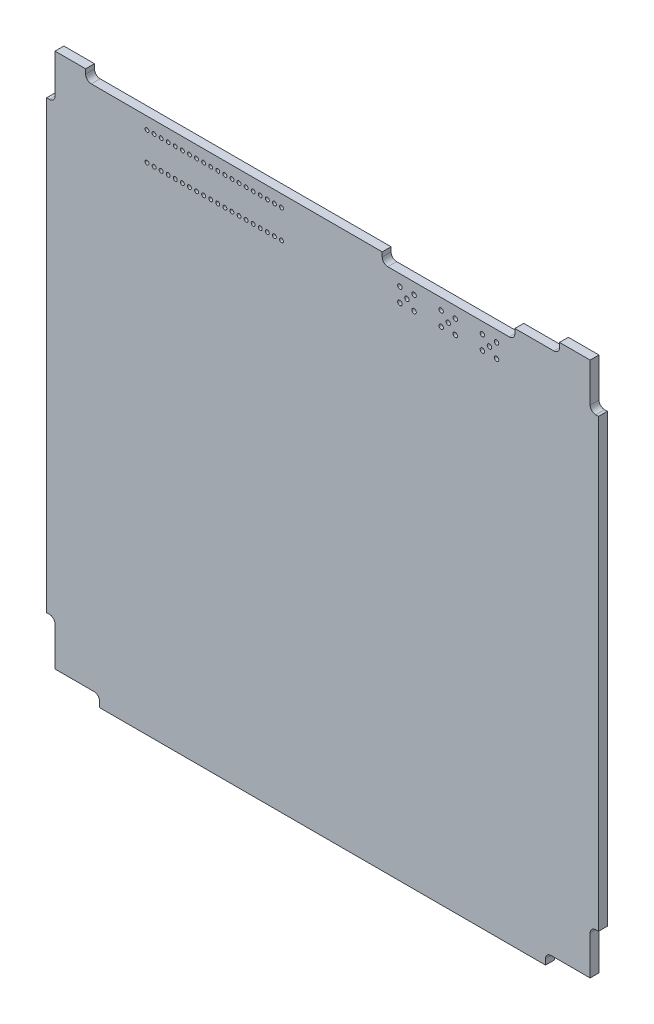
SolidWorks part; units mm, degrees
material "ABS"
ref_plane "Front Plane" through (0, 0, 0) normal (0, 0, 1) x (1, 0, 0)
ref_plane "Top Plane" through (0, 0, 0) normal (0, 1, 0) x (1, 0, 0)
ref_plane "Right Plane" through (0, 0, 0) normal (1, 0, 0) x (0, 0, -1)
sketch "Sketch1" plane through (0, 0, 0) normal (0, 0, 1) x (1, 0, 0)
  line L0 (-40, 50) -> (-40, 48)
  line L1 (-50, -50) -> (50, -50)
  line L2 (-50, -50) -> (-50, 50)
  line L3 (-50, 50) -> (50, 50)
  line L4 (50, -50) -> (50, 50)
  line L5 (-50, -50) -> (50, 50) construction
  line L6 (-50, 50) -> (50, -50) construction
  line L7 (-50, 50) -> (-40, 50)
  line L8 (-50, 50) -> (-50, 40)
  line L9 (-40, 48) -> (-48, 48)
  line L10 (-48, 48) -> (-48, 40)
  line L11 (50, 50) -> (40, 50)
  line L12 (50, 50) -> (50, 40)
  line L13 (-48, 40) -> (-50, 40)
  line L14 (50, 40) -> (48, 40)
  line L15 (-50, -50) -> (-37.8649, -50)
  line L16 (-50, -50) -> (-50, -37.8649)
  line L17 (50, 50) -> (50, 40)
  line L18 (50, 50) -> (40, 50)
  line L19 (50, -50) -> (41.5, -50)
  line L20 (50, -50) -> (50, -41.5)
  line L21 (48, 40) -> (48, 48)
  line L22 (48, 48) -> (40, 48)
  line L23 (40, 48) -> (40, 50)
  line L24 (40, -50) -> (40, -48)
  line L25 (50, -50) -> (40, -50)
  line L26 (50, -50) -> (50, -40)
  line L27 (40, -48) -> (48, -48)
  line L28 (48, -48) -> (48, -40)
  line L29 (48, -40) -> (50, -40)
  line L30 (-50, -40) -> (-48, -40)
  line L31 (-50, -50) -> (-50, -40)
  line L32 (-50, -50) -> (-40, -50)
  line L33 (-48, -40) -> (-48, -48)
  line L34 (-48, -48) -> (-40, -48)
  line L35 (-40, -48) -> (-40, -50)
  point P0 (0, 0)
  point P38 (0, 0)
  dimension "D1" = 100
  dimension "D2" = 100
  dimension "D3" = 2
  dimension "D4" = 10
  dimension "D5" = 4
extrude "Boss-Extrude1" add sketch "Sketch1" along normal blind 1.5875 contours L1 L4 L3 L2 region at (0, 0, 0)
sketch "Sketch2" plane through (0, 0, 1.5875) normal (0, 0, 1) x (1, 0, 0)
  line L0 (0, 50) -> (0, -50) construction
  line L1 (-40, 50) -> (40, 50) construction
  line L2 (-40, -50) -> (40, -50) construction
  line L3 (-50, -40) -> (-50, 40) construction
  line L4 (-40, 50) -> (40, 50) construction
  circle A0 centre (-31.5, 44) radius 0.35
  circle A1 centre (-30.23, 44) radius 0.35
  circle A2 centre (-28.96, 44) radius 0.35
  circle A3 centre (-27.69, 44) radius 0.35
  circle A4 centre (-26.42, 44) radius 0.35
  circle A5 centre (-25.15, 44) radius 0.35
  circle A6 centre (-23.88, 44) radius 0.35
  circle A7 centre (-22.61, 44) radius 0.35
  circle A8 centre (-21.34, 44) radius 0.35
  circle A9 centre (-20.07, 44) radius 0.35
  circle A10 centre (-18.8, 44) radius 0.35
  circle A11 centre (-17.53, 44) radius 0.35
  circle A12 centre (-16.26, 44) radius 0.35
  circle A13 centre (-14.99, 44) radius 0.35
  circle A14 centre (-13.72, 44) radius 0.35
  circle A15 centre (-12.45, 44) radius 0.35
  circle A16 centre (-11.18, 44) radius 0.35
  circle A17 centre (-9.91, 44) radius 0.35
  circle A18 centre (-8.64, 44) radius 0.35
  circle A19 centre (-7.37, 44) radius 0.35
  circle A20 centre (-30.23, 38.92) radius 0.35
  circle A21 centre (-28.96, 38.92) radius 0.35
  circle A22 centre (-27.69, 38.92) radius 0.35
  circle A23 centre (-26.42, 38.92) radius 0.35
  circle A24 centre (-25.15, 38.92) radius 0.35
  circle A25 centre (-23.88, 38.92) radius 0.35
  circle A26 centre (-22.61, 38.92) radius 0.35
  circle A27 centre (-21.34, 38.92) radius 0.35
  circle A28 centre (-20.07, 38.92) radius 0.35
  circle A29 centre (-18.8, 38.92) radius 0.35
  circle A30 centre (-17.53, 38.92) radius 0.35
  circle A31 centre (-16.26, 38.92) radius 0.35
  circle A32 centre (-14.99, 38.92) radius 0.35
  circle A33 centre (-13.72, 38.92) radius 0.35
  circle A34 centre (-12.45, 38.92) radius 0.35
  circle A35 centre (-11.18, 38.92) radius 0.35
  circle A36 centre (-9.91, 38.92) radius 0.35
  circle A37 centre (-8.64, 38.92) radius 0.35
  circle A38 centre (-7.37, 38.92) radius 0.35
  circle A39 centre (-31.5, 38.92) radius 0.35
  dimension "D1" = 0.7
  dimension "D4" = 18.5
  dimension "D5" = 6
  dimension "D2" = 5.08
  dimension "D3" = 1.27
extrude "Cut-Extrude1" cut sketch "Sketch2" against normal through all
sketch "Sketch3" plane through (0, 50, 0) normal (0, 1, 0) x (1, 0, 0)
  line L0 (-40, 0) -> (40, 0) construction
  line L1 (10.7, 0) -> (19.7, 0)
  line L2 (10.7, 0) -> (10.7, -1.5875)
  line L3 (10.7, -1.5875) -> (19.7, -1.5875)
  line L4 (-40, -1.5875) -> (-40, 0) construction
  line L5 (-40, -1.5875) -> (40, -1.5875) construction
  line L6 (15.2, 0) -> (15.2, -1.5875) construction
  line L7 (12, 0) -> (12, -1.5875) construction
  line L8 (18.4, 0) -> (18.4, -1.5875) construction
  line L9 (-40, -1.5875) -> (40, -1.5875) construction
  line L12 (19.7, 0) -> (34.5, 0)
  line L14 (19.7, -1.5875) -> (34.5, -1.5875)
  line L15 (34.5, 0) -> (34.5, -1.5875)
  dimension "D1" = 9
  dimension "D2" = 6.4
  dimension "D3" = 3.2
  dimension "D5" = 14.8
  dimension "D6" = 50.7
extrude "Cut-Extrude2" cut sketch "Sketch3" against normal blind 5.6475
fillet "Fillet2" radius 1 2 edges at (10.7, 44.3525, 0.7938) (34.5, 44.3525, 0.7937)
sketch "Sketch5" plane through (0, 0, 0) normal (0, 0, -1) x (-1, 0, 0)
  line L0 (40, -50) -> (-40, -50) construction
  line L1 (-49.5, 50) -> (49.5, 50)
  line L2 (-49.5, 50) -> (-49.5, -50)
  line L3 (-49.5, -50) -> (49.5, -50)
  line L4 (49.5, 50) -> (49.5, -50)
  line L5 (40, 50) -> (-10.7, 50) construction
  line L6 (50, -40) -> (50, 40) construction
  dimension "D1" = 99
  dimension "D2" = 0.5
extrude "Cut-Extrude3" cut sketch "Sketch5" against normal through all flip side to cut
sketch "Sketch6" plane through (0, 0, 1.5875) normal (0, 0, 1) x (1, 0, 0)
  line L0 (11.7, 44.3525) -> (33.5, 44.3525) construction
  line L1 (28.67, 39.8125) -> (31.21, 39.8125) construction
  line L2 (28.67, 39.8125) -> (28.67, 42.3525) construction
  line L3 (28.67, 42.3525) -> (31.21, 42.3525) construction
  line L4 (31.21, 39.8125) -> (31.21, 42.3525) construction
  line L5 (28.67, 39.8125) -> (31.21, 42.3525) construction
  line L6 (28.67, 42.3525) -> (31.21, 39.8125) construction
  line L7 (34.5, 45.3525) -> (34.5, 50) construction
  line L8 (21.27, 39.8125) -> (23.81, 39.8125) construction
  line L9 (21.27, 39.8125) -> (21.27, 42.3525) construction
  line L10 (21.27, 42.3525) -> (23.81, 42.3525) construction
  line L11 (23.81, 39.8125) -> (23.81, 42.3525) construction
  line L12 (21.27, 39.8125) -> (23.81, 42.3525) construction
  line L13 (21.27, 42.3525) -> (23.81, 39.8125) construction
  line L14 (13.87, 39.8125) -> (16.41, 39.8125) construction
  line L17 (13.87, 39.8125) -> (13.87, 42.3525) construction
  line L18 (13.87, 42.3525) -> (16.41, 42.3525) construction
  line L19 (16.41, 39.8125) -> (16.41, 42.3525) construction
  line L20 (13.87, 39.8125) -> (16.41, 42.3525) construction
  line L21 (13.87, 42.3525) -> (16.41, 39.8125) construction
  circle A0 centre (29.94, 41.0825) radius 0.4
  circle A1 centre (28.67, 42.3525) radius 0.4
  circle A2 centre (31.21, 42.3525) radius 0.4
  circle A3 centre (31.21, 39.8125) radius 0.4
  circle A4 centre (28.67, 39.8125) radius 0.4
  circle A5 centre (22.54, 41.0825) radius 0.4
  circle A6 centre (21.27, 42.3525) radius 0.4
  circle A7 centre (23.81, 42.3525) radius 0.4
  circle A8 centre (23.81, 39.8125) radius 0.4
  circle A9 centre (21.27, 39.8125) radius 0.4
  circle A10 centre (15.14, 41.0825) radius 0.4
  circle A11 centre (13.87, 42.3525) radius 0.4
  circle A12 centre (16.41, 42.3525) radius 0.4
  circle A13 centre (16.41, 39.8125) radius 0.4
  circle A14 centre (13.87, 39.8125) radius 0.4
  point P23 (27.2, 39.7784)
  point P32 (19.8, 39.7784)
  dimension "D1" = 2.54
  dimension "D2" = 0.8
  dimension "D3" = 2.54
  dimension "D4" = 3.27
  dimension "D5" = 4.56
  dimension "D6" = 7.4
  dimension "D8" = 2
  dimension "D7" = 3
sketch "Sketch7" plane through (0, 0, 1.5875) normal (0, 0, 1) x (1, 0, 0)
  line L0 (-40, 50) -> (-36.5, 50)
  line L1 (-40, 50) -> (10.7, 50) construction
  line L2 (-36.5, 50) -> (-36.5, 48)
  line L3 (-36.5, 48) -> (-41.5, 48)
  line L4 (-40, 48) -> (-48, 48) construction
  line L5 (-41.5, 48) -> (-41.5, 41.5)
  line L6 (-41.5, 41.5) -> (-42, 41.5)
  line L7 (-47, 36.5) -> (-47, -36.5)
  line L8 (-40, 50) -> (-49.5, 50)
  line L9 (-49.5, 50) -> (-49.5, -50)
  line L10 (-49.5, -40) -> (-49.5, 40) construction
  line L11 (49.5, 0) -> (-49.5, 0) construction
  line L12 (-40, -50) -> (-49.5, -50)
  line L13 (-41.5, -41.5) -> (-42, -41.5)
  line L14 (-41.5, -48) -> (-41.5, -41.5)
  line L15 (-36.5, -48) -> (-41.5, -48)
  line L16 (-36.5, -50) -> (-36.5, -48)
  line L17 (-40, -50) -> (-36.5, -50)
  line L18 (0, 0) -> (0, -14.0383) construction
  line L19 (40, -50) -> (36.5, -50)
  line L20 (36.5, -50) -> (36.5, -48)
  line L21 (36.5, -48) -> (41.5, -48)
  line L22 (41.5, -48) -> (41.5, -41.5)
  line L23 (41.5, -41.5) -> (42, -41.5)
  line L24 (40, -50) -> (49.5, -50)
  line L25 (49.5, 50) -> (49.5, -50)
  line L26 (40, 50) -> (49.5, 50)
  line L27 (47, 36.5) -> (47, -36.5)
  line L28 (41.5, 41.5) -> (42, 41.5)
  line L29 (41.5, 48) -> (41.5, 41.5)
  line L30 (36.5, 48) -> (41.5, 48)
  line L31 (36.5, 50) -> (36.5, 48)
  line L32 (40, 50) -> (36.5, 50)
  arc A0 (-42, 41.5) -> (-47, 36.5) centre (-42, 36.5) ccw
  arc A1 (-42, -41.5) -> (-47, -36.5) centre (-42, -36.5) cw
  arc A2 (42, -41.5) -> (47, -36.5) centre (42, -36.5) ccw
  arc A3 (42, 41.5) -> (47, 36.5) centre (42, 36.5) cw
  point P25 (-47, 0)
  point P32 (0, 0)
  point P50 (47, 0)
  dimension "D1" = 5
  dimension "D2" = 13
  dimension "D3" = 8
  dimension "D4" = 8.5
  dimension "D5" = 2.5
  dimension "D6" = 5
sketch "Sketch8" plane through (0, 50, 0) normal (0, 1, 0) x (1, 0, 0)
  line L0 (34.5, -1.5875) -> (40, -1.5875) construction
  line L1 (-42.5, 0) -> (42.5, 0)
  line L2 (-42.5, 0) -> (-42.5, -1.5875)
  line L3 (-42.5, -1.5875) -> (42.5, -1.5875)
  line L4 (42.5, 0) -> (42.5, -1.5875)
  line L5 (-42.5, 0) -> (42.5, -1.5875) construction
  line L6 (-42.5, -1.5875) -> (42.5, 0) construction
  line L8 (-40, -1.5875) -> (-40, 0) construction
  point P0 (0, -0.7937)
  dimension "D1" = 85
  dimension "D2" = 1.5875
  dimension "D3" = 2.5
extrude "Cut-Extrude4" cut sketch "Sketch8" against normal blind 3.8375
fillet "Fillet1" radius 1 8 edges at (-48, -40, 0.7937) (-40, -48, 0.7937) (40, -48, 0.7937) (48, -40, 0.7937) (48, 40, 0.7937) (-48, 40, 0.7937) (42.5, 46.1625, 0.7937) (-42.5, 46.1625, 0.7937)
sketch "Sketch10" plane through (0, 0, 1.5875) normal (0, 0, 1) x (1, 0, 0)
  line L0 (-41.5, 48) -> (-41.5, 41.5) construction
  line L1 (-41.5, 48) -> (41.5, 48)
  line L2 (-41.5, 48) -> (-41.5, 46.4125)
  line L3 (-41.5, 46.4125) -> (41.5, 46.4125)
  line L4 (41.5, 48) -> (41.5, 46.4125)
  line L5 (-41.5, 48) -> (41.5, 46.4125) construction
  line L6 (-41.5, 46.4125) -> (41.5, 48) construction
  line L7 (-36.5, 48) -> (-41.5, 48) construction
  point P0 (0, 47.2062)
  dimension "D1" = 83
  dimension "D2" = 1.5875
extrude "Cut-Extrude5" cut sketch "Sketch6" against normal through all
